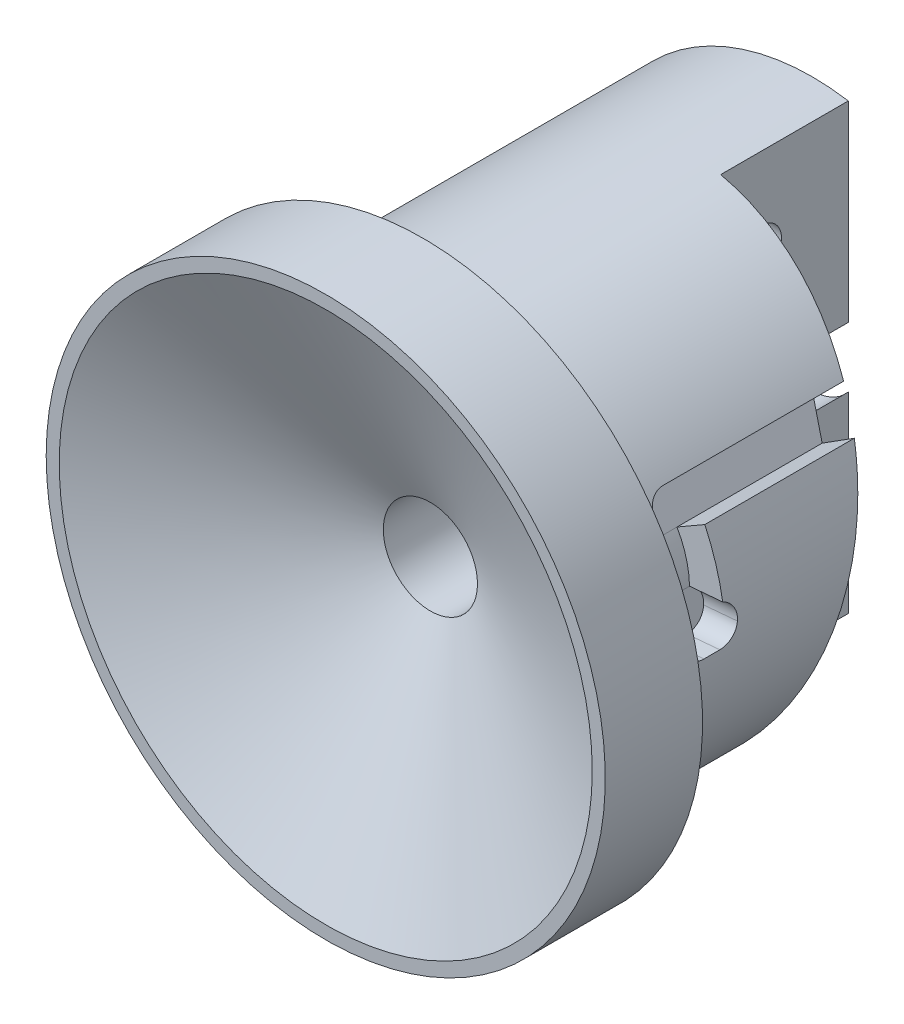
SolidWorks part; units mm, degrees
material "A-2 Steel"
ref_plane "Alzado" through (0, 0, 0) normal (0, 0, 1) x (1, 0, 0)
ref_plane "Planta" through (0, 0, 0) normal (0, 1, 0) x (1, 0, 0)
ref_plane "Vista lateral" through (0, 0, 0) normal (1, 0, 0) x (0, 0, -1)
sketch "Croquis2" plane through (0, 0, 0) normal (1, 0, 0) x (0, 0, -1)
  line L0 (0.3255, 0) -> (-7.0214, 0) construction
  line L1 (0, 3.0734) -> (31.75, 3.0734)
  line L2 (31.75, 3.0734) -> (31.75, 14.6812)
  line L3 (31.75, 14.6812) -> (6.35, 14.6812)
  line L4 (6.35, 14.6812) -> (6.35, 18.2499)
  line L5 (6.35, 18.2499) -> (0, 18.2499)
  line L6 (0, 18.2499) -> (0, 3.0734)
  dimension "D1" = 6.1468
  dimension "D2" = 36.4998
  dimension "D3" = 31.75
  dimension "D4" = 25.4
  dimension "D5" = 29.3624
revolve "Revolución1" add sketch "Croquis2" angle 360 about L0
sketch "Croquis3" plane through (0, 0, 0) normal (0, 1, 0) x (1, 0, 0)
  line L0 (0, 8.2982) -> (-17.399, 0)
  line L2 (-18.2499, 0) -> (18.2499, 0) construction
  line L3 (-17.399, 0) -> (0, 0)
  line L4 (0, 0) -> (0, 8.2982)
  line L5 (0, 0) -> (0, -3.613) construction
  dimension "D1" = 3.613
  dimension "D2" = 34.798
  dimension "D3" = 8.2982
revolve "Cortar-Revolución1" cut sketch "Croquis3" angle 360 about L5
sketch "Croquis4" plane through (0, 0, -31.75) normal (0, 0, -1) x (-1, 0, 0)
  line L0 (-2.3622, -14.4899) -> (-2.3622, 14.4899)
  circle A1 centre (0, 0) radius 14.6812 construction
  circle A3 centre (0, 0) radius 14.6812
  arc A4 (-2.3622, 14.4899) -> (-2.3622, -14.4899) centre (0, 0) ccw
  dimension "D1" = 2.3622
  dimension "D2" = 0
ref_plane "Plano1" through (2.3622, 0, 0) normal (-1, 0, 0) x (0, 1, 0)
sketch "Croquis5" plane through (2.3622, 0, 0) normal (-1, 0, 0) x (0, 1, 0)
  line L0 (14.4899, 23.4188) -> (-14.4899, 15.6537)
  line L1 (14.4899, 31.75) -> (-14.4899, 31.75) construction
  line L4 (-14.4899, 31.75) -> (-14.4899, 15.6537)
  line L6 (14.4899, 23.4188) -> (14.4899, 31.75)
  line L7 (-14.4899, 31.75) -> (14.4899, 31.75) construction
  line L8 (14.4899, 31.75) -> (-14.4899, 31.75)
  dimension "D1" = 15
  dimension "D2" = 8.3312
extrude "Cortar-Extruir1" cut sketch "Croquis5" against normal through all
hole_wizard "Taladro roscado #6-321" positions "Croquis6" profile "Croquis7" tap size "#6-32" standard "Ansi Inch"
sketch "Croquis6" plane through (2.3622, 0, 0) normal (1, 0, 0) x (0, 0, -1)
  line L0 (26.0341, 8.9408) -> (31.75, 8.9408) construction
  line L1 (31.75, -14.4899) -> (31.75, 14.4899) construction
  line L3 (0, 0) -> (31.75, 0) construction
  line L5 (20.0631, 1.9662) -> (23.4188, 14.4899) construction
  point P0 (26.0341, 8.9408)
  dimension "D1" = 8.9408
  dimension "D2" = 3.9624
sketch "Croquis7" plane through (2.3622, 8.9408, -26.0341) normal (0, 1, 0) x (0, 0, -1)
  line L0 (0, 0) -> (0, 11.7855)
  line L1 (0, 11.7855) -> (1.3525, 10.9728)
  line L2 (1.3525, 10.9728) -> (1.3525, 0)
  line L5 (1.3525, 0) -> (0, 0)
  line L10 (0, 11.7855) -> (-1.3526, 10.9728) construction
  line L11 (0, -6.35) -> (0, 107.95) construction
  dimension "Diámetro de perforador para roscar" = 2.7051
  dimension "Profundidad de perforador para roscar" = 10.9728
  dimension "Ángulo de perforador" = 118
cosmetic thread "Rosca de taladro1" parameters "D1"=7.0104, "D2"=3.5052
sketch "Croquis8" plane through (0, 0, -31.75) normal (0, 0, -1) x (-1, 0, 0)
  line L0 (-13.3178, 6.1786) -> (-11.4986, 5.1283)
  line L1 (-11.4986, 5.1283) -> (-10.1905, 7.3939)
  line L2 (-10.1905, 7.3939) -> (-12.0097, 8.4443)
  line L3 (0, 0) -> (-18.2499, 0) construction
  line L4 (0, 0) -> (-15.8049, 9.125) construction
  arc A0 (-2.3622, 14.4899) -> (-2.3622, -14.4899) centre (0, 0) ccw construction
  arc A1 (-12.0097, 8.4443) -> (-13.3178, 6.1786) centre (0, 0) ccw
  circle A2 centre (0, 0) radius 18.2499 construction
  point P12 (-10.8445, 6.2611)
  point P13 (-12.7143, 7.3406)
  dimension "D1" = 30
  dimension "D2" = 2.6162
  dimension "D3" = 2.159
extrude "Cortar-Extruir2" cut sketch "Croquis8" against normal offset from surface (22.9362 mm away) 2.4638 up to face at (-18.2499, 0, -6.35)
sketch "Croquis9" plane through (0, 0, -8.8138) normal (0, 0, -1) x (-1, 0, 0)
  line L0 (-10.8445, 6.2611) -> (0, 0) construction
  line L1 (-10.1905, 7.3939) -> (-11.4986, 5.1283) construction
  line L2 (0, 0) -> (-18.2499, 0) construction
  line L3 (0, 0) -> (-18.1805, 1.5906) construction
  line L5 (-12.3024, 2.3894) -> (-12.5304, -0.2168)
  line L6 (-12.5304, -0.2168) -> (-14.6812, -0.0287)
  line L7 (-11.0956, 5.8262) -> (-11.4986, 5.1283) construction
  line L8 (-11.0956, 5.8262) -> (-12.9579, 6.9014)
  circle A0 centre (0, 0) radius 18.2499 construction
  arc A1 (-13.3178, 6.1786) -> (-2.3622, -14.4899) centre (0, 0) ccw construction
  circle A2 centre (0, 0) radius 14.6812 construction
  arc A3 (-13.7662, 5.102) -> (-14.6812, -0.0287) centre (0, 0) ccw construction
  arc A4 (-11.0956, 5.8262) -> (-12.3024, 2.3894) centre (0, 0) ccw
  arc A5 (-12.9579, 6.9014) -> (-14.6812, -0.0287) centre (0, 0) ccw
  arc A6 (-12.0097, 8.4443) -> (-13.3178, 6.1786) centre (0, 0) ccw construction
  point P12 (-12.4164, 1.0863)
  point P15 (-14.4532, 2.5776)
  arc M11 (-12.0097, 8.4443) -> (-13.3178, 6.1786) centre (0, 0) ccw
  line M12 (-13.3178, 6.1786) -> (-11.4986, 5.1283)
  line M13 (-11.4986, 5.1283) -> (-10.1905, 7.3939)
  dimension "D1" = 25
  dimension "D2" = 2.6162
  dimension "D3" = 2.159
  dimension "D4" = 2.159
extrude "Cortar-Extruir3" cut sketch "Croquis9" along normal blind 2.6162 contours A5 L6 L5 A4 M12 M13 | L8 M13 M11 M12 region at (13.2214, 2.7992, -8.8138) region at (12.2183, 6.0109, -8.8138)
sketch "Croquis10" plane through (12.4164, 1.0863, 0) normal (0.9962, 0.0872, 0) x (0, 0, -1)
  line L0 (8.8138, 1.3081) -> (8.8138, -1.3081) construction
  line L1 (12.2428, -0.0974) -> (10.9347, -0.0974) construction
  line L3 (11.43, -1.3081) -> (11.43, 1.1133)
  arc A0 (11.43, -1.3081) -> (11.43, 1.1133) centre (10.9347, -0.0974) ccw
  dimension "D1" = 3.429
  dimension "D2" = 2.6162
extrude "Cortar-Extruir4" cut sketch "Croquis10" along normal through all
fillet "Redondeo1" radius 1.1938 2 edges at (11.1001, 7.9191, -8.8138) (13.6058, -0.1227, -8.8138)
sketch "Croquis11" plane through (0, 0, -11.43) normal (0, 0, 1) x (1, 0, 0)
  line L0 (10.1905, 7.3939) -> (11.4986, 5.1283) construction
  line L1 (11.0956, 5.8262) -> (11.4986, 5.1283)
  line L2 (12.5304, -0.2168) -> (12.3193, 2.1954) construction
  line L3 (12.3024, 2.3894) -> (12.3193, 2.1954)
  arc A0 (12.3193, 2.1954) -> (11.4986, 5.1283) centre (6.1834, 2.0595) ccw
  arc A10 (12.3024, 2.3894) -> (11.0956, 5.8262) centre (0, 0) ccw
  arc A11 (12.3024, 2.3894) -> (11.0956, 5.8262) centre (0, 0) ccw construction
extrude "Saliente-Extruir1" add sketch "Croquis11" along normal up to surface (2.6162 mm away) up to face at (12.3975, 4.0516, -8.8138)
fillet "Redondeo2" radius 1.1938 1 edges at (13.6058, -0.1227, -11.43)
